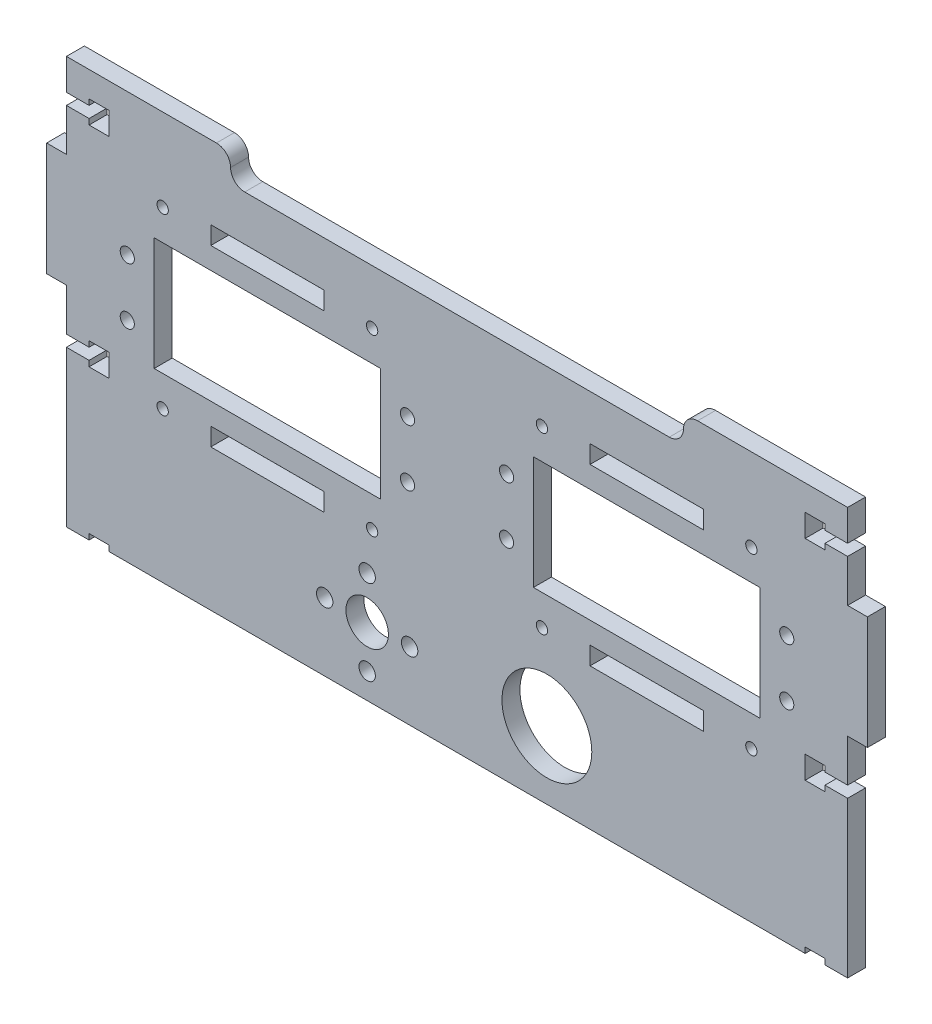
SolidWorks part; units mm, degrees
ref_plane "Front Plane" through (0, 0, 0) normal (0, 0, 1) x (1, 0, 0)
ref_plane "Top Plane" through (0, 0, 0) normal (0, 1, 0) x (1, 0, 0)
ref_plane "Right Plane" through (0, 0, 0) normal (1, 0, 0) x (0, 0, -1)
sketch "Sketch1" plane through (0, 0, 0) normal (0, 0, 1) x (1, 0, 0)
  line L0 (-69, -10) -> (-69, -27)
  line L5 (-69, 25) -> (69, 25)
  line L6 (-69, 25) -> (-69, 10)
  line L7 (-69, -27) -> (69, -27)
  line L8 (69, 25) -> (69, 10)
  line L9 (-69, -10) -> (-72.5, -10)
  line L11 (-69, 10) -> (-72.5, 10)
  line L12 (-72.5, -10) -> (-72.5, 10)
  line L13 (69, 10) -> (72.5, 10)
  line L15 (69, -10) -> (72.5, -10)
  line L16 (72.5, 10) -> (72.5, -10)
  line L17 (69, -10) -> (69, -27)
  point P13 (-72.5, 0)
  point P14 (72.5, 0)
  dimension "D1" = 52
  dimension "D2" = 138
  dimension "D3" = 69
  dimension "D4" = 27
  dimension "D5" = 20
  dimension "D6" = 3.5
  dimension "D7" = 0
  dimension "D8" = 20
  dimension "D9" = 3.5
  dimension "D10" = 0
extrude "Boss-Extrude1" add sketch "Sketch1" against normal blind 3.175
sketch "Sketch2" plane through (0, 0, 0) normal (0, 0, 1) x (1, 0, 0)
  line L0 (-69, 19.5) -> (-65, 19.5)
  line L2 (-65, 19.5) -> (-65, 20.5)
  line L3 (-65, 20.5) -> (-61.5, 20.5)
  line L4 (-61.5, 20.5) -> (-61.5, 16.5)
  line L5 (-61.5, 16.5) -> (-65, 16.5)
  line L6 (-65, 16.5) -> (-65, 17.5)
  line L7 (-65, 17.5) -> (-69, 17.5)
  line L8 (-69, 17.5) -> (-69, 19.5)
  line L10 (-69, 25) -> (-69, 10) construction
  point P2 (-69, 18.5)
  dimension "D1" = 4
  dimension "D2" = 3.5
  dimension "D3" = 2
  dimension "D4" = 2
  dimension "D5" = 3.5
  dimension "D6" = 7.5
  dimension "D7" = 18.5
  dimension "D8" = 0
extrude "Cut-Extrude1" cut sketch "Sketch2" against normal through all both and the other way through all
ref_plane "Plane3" through (0, 0, 0) normal (0, 1, 0) x (1, 0, 0)
ref_plane "Plane4" through (0, 0, 0) normal (-1, 0, 0) x (0, 0, 1)
mirror "Mirror1" about plane through (0, 0, 0) normal (-1, 0, 0) of "Cut-Extrude1"
mirror "Mirror2" about plane through (0, 0, 0) normal (0, 1, 0) of "Mirror1", "Cut-Extrude1"
sketch "Sketch4" plane through (0, 0, 0) normal (0, 0, 1) x (1, 0, 0)
  line L0 (69, -27) -> (69, -19.5) construction
  line L1 (-69, -27) -> (69, -27)
  line L2 (-69, -27) -> (-69, -47)
  line L3 (-69, -47) -> (69, -47)
  line L4 (69, -27) -> (69, -47)
  line L5 (-69, -19.5) -> (-69, -27) construction
  line L6 (-69, -27) -> (69, -27) construction
  dimension "D1" = 20
  dimension "D2" = 0
  dimension "D3" = 0
  dimension "D4" = 0
extrude "Boss-Extrude3" add sketch "Sketch4" against normal up to surface (3.175 mm away) up to face at (0, -0.0909, -3.175)
sketch "Sketch5" plane through (0, 0, 0) normal (0, 0, 1) x (1, 0, 0)
  line L0 (69, 25) -> (-69, 25) construction
  line L1 (-40, 25) -> (40, 25)
  line L2 (-40, 25) -> (-40, 20)
  line L3 (-40, 20) -> (40, 20)
  line L4 (40, 25) -> (40, 20)
  point P4 (0, 25)
  point P7 (0, 25)
  dimension "D1" = 80
  dimension "D2" = 0
  dimension "D3" = 0
  dimension "D4" = 5
extrude "Cut-Extrude2" cut sketch "Sketch5" against normal through all both and the other way through all
fillet "Fillet1" radius 2.5 4 edges at (40, 20, -1.5875) (40, 25, -1.5875) (-40, 20, -1.5875) (-40, 25, -1.5875)
sketch "Sketch6" plane through (0, 0, 0) normal (0, 0, 1) x (1, 0, 0)
  line L0 (-69, -47) -> (69, -47) construction
  line L1 (61.5, -47) -> (65, -47)
  line L2 (61.5, -47) -> (61.5, -46)
  line L3 (61.5, -46) -> (65, -46)
  line L4 (65, -47) -> (65, -46)
  line L5 (65, -19.5) -> (65, -20.5) construction
  line L6 (61.5, -20.5) -> (61.5, -16.5) construction
  dimension "D1" = 0
  dimension "D2" = 0
  dimension "D3" = 1
extrude "Cut-Extrude3" cut sketch "Sketch6" against normal through all both and the other way through all
mirror "Mirror3" about plane through (0, 0, 0) normal (-1, 0, 0) of "Cut-Extrude3"
sketch "Sketch10" plane through (0, 0, -3.175) normal (0, 0, -1) x (-1, 0, 0)
  line L0 (37.5, 20) -> (-37.5, 20) construction
  line L1 (53.5, -15) -> (13.5, -15)
  line L2 (53.5, -15) -> (53.5, 5)
  line L3 (53.5, 5) -> (13.5, 5)
  line L4 (13.5, -15) -> (13.5, 5)
  line L5 (61.5, -16.5) -> (61.5, -20.5) construction
  dimension "D1" = 20
  dimension "D2" = 40
  dimension "D3" = 15
  dimension "D4" = 8
extrude "Cut-Extrude4" cut sketch "Sketch10" against normal through all
sketch "Sketch11" plane through (0, 0, -3.175) normal (0, 0, -1) x (-1, 0, 0)
  line L16 (52.0472, -20.41) -> (4.3904, -20.41) construction
  line L17 (13.5, -15) -> (53.5, -15) construction
  line L18 (23.5, -18.82) -> (43.5, -18.82)
  line L19 (23.5, -18.82) -> (23.5, -22)
  line L20 (23.5, -22) -> (43.5, -22)
  line L21 (43.5, -18.82) -> (43.5, -22)
  line L22 (23.5, -18.82) -> (43.5, -22) construction
  line L23 (23.5, -22) -> (43.5, -18.82) construction
  line L24 (13.5, 5) -> (13.5, -15) construction
  circle A2 centre (15, -20.41) radius 1
  circle A3 centre (52, -20.41) radius 1
  point P6 (55.91, -8)
  point P20 (33.5, -20.41)
  dimension "D13" = 2
  dimension "D14" = 2
  dimension "D16" = 8.5
  dimension "D9" = 7
  dimension "D10" = 20
  dimension "D11" = 3.18
  dimension "D12" = 20
  dimension "D15" = 8.5
extrude "Cut-Extrude5" cut sketch "Sketch11" against normal through all
sketch "Sketch12" plane through (0, 0, -3.175) normal (0, 0, -1) x (-1, 0, 0)
  line L5 (0, -10) -> (57.6643, -10) construction
  line L6 (13.5, -15) -> (53.5, -15) construction
  line L7 (13.5, 5) -> (13.5, -15) construction
  line L8 (53.5, -15) -> (53.5, 5) construction
  circle A2 centre (8.75, -10) radius 1.25
  circle A4 centre (58.25, -10) radius 1.25
  dimension "D7" = 4.75
  dimension "D8" = 4.75
  dimension "D9" = 2.5
  dimension "D10" = 2.5
  dimension "D6" = 5
extrude "Cut-Extrude6" cut sketch "Sketch12" against normal through all
ref_plane "Plane5" through (-29.5, 0, 0) normal (1, 0, 0) x (0, 0, -1)
ref_plane "Plane6" through (0, -5, 0) normal (0, 1, 0) x (1, 0, 0)
mirror "Mirror4" about plane through (0, -5, 0) normal (0, 1, 0) of "Cut-Extrude5", "Cut-Extrude6"
mirror "Mirror5" about plane through (0, 0, 0) normal (-1, 0, 0) of "Cut-Extrude4", "Mirror4"
sketch "Sketch13" plane through (0, 0, 0) normal (0, 0, 1) x (1, 0, 0)
  line L0 (-13.5, -15) -> (-53.5, -15) construction
  line L1 (-15.875, -35) -> (18.3958, -35) construction
  line L2 (0, 1.7463) -> (0, -1.7463) construction
  circle A0 centre (-15.875, -35) radius 3.75
  circle A1 centre (15.875, -35) radius 7.9375
  dimension "D2" = 7.5
  dimension "D3" = 15.875
  dimension "D5" = 15.875
  dimension "D1" = 20
  dimension "D4" = 31.75
extrude "Cut-Extrude7" cut sketch "Sketch13" against normal through all
sketch "Sketch14" plane through (0, 0, 0) normal (0, 0, 1) x (1, 0, 0)
  line L0 (-15.875, -35) -> (-22.6021, -35) construction
  circle A0 centre (-23.375, -35) radius 1.45
  circle A1 centre (-15.875, -27.5) radius 1.45
  circle A2 centre (-8.375, -35) radius 1.45
  circle A3 centre (-15.875, -42.5) radius 1.45
  dimension "D1" = 2.9
  dimension "D2" = 7.5
  dimension "D3" = 4
extrude "Cut-Extrude8" cut sketch "Sketch14" against normal through all
